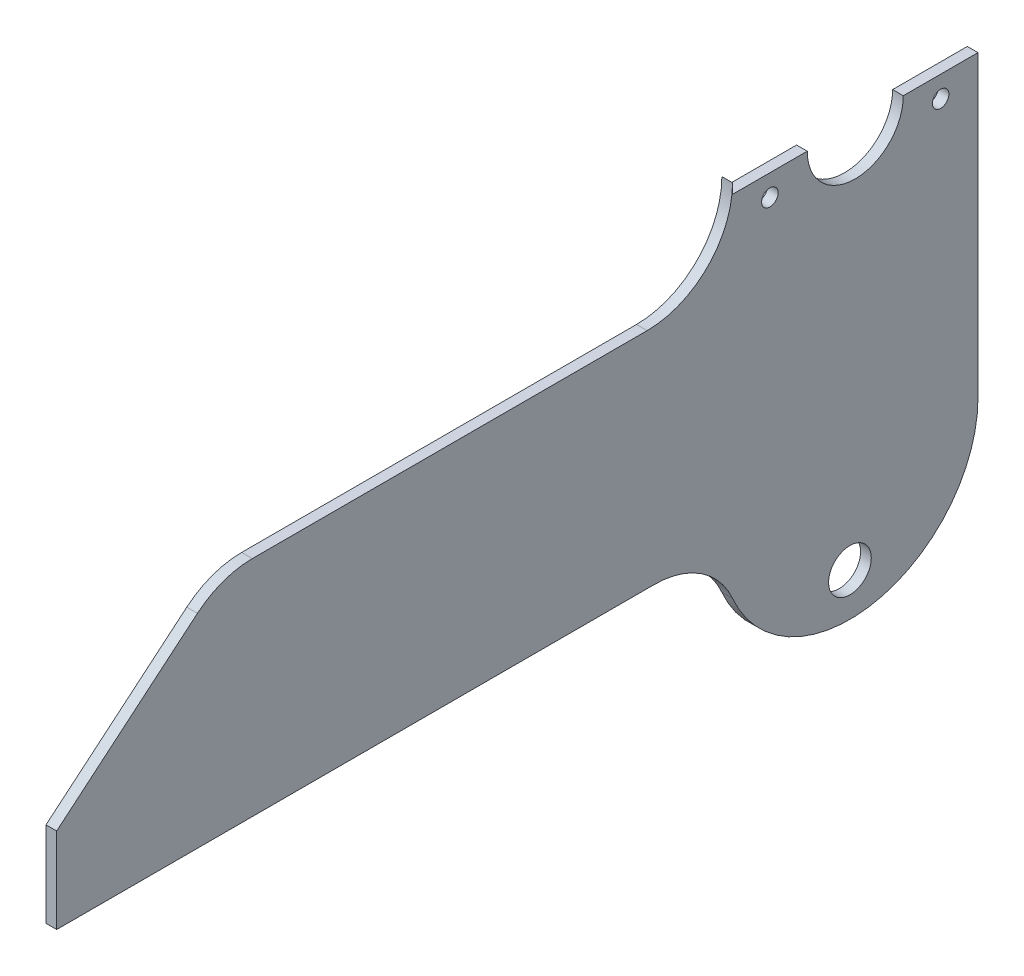
SolidWorks part; units mm, degrees
material "6061 Alloy"
ref_plane "Front Plane" through (0, 0, 0) normal (0, 0, 1) x (1, 0, 0)
ref_plane "Top Plane" through (0, 0, 0) normal (0, 1, 0) x (1, 0, 0)
ref_plane "Right Plane" through (0, 0, 0) normal (1, 0, 0) x (0, 0, -1)
sketch "Sketch1" plane through (0, 0, 0) normal (1, 0, 0) x (0, 0, -1)
  line L0 (0, -44.45) -> (0, 44.45)
  line L7 (0, 44.45) -> (-22.225, 44.45)
  line L8 (-50.8, 44.45) -> (-73.025, 44.45)
  line L10 (-98.425, 22.0322) -> (-215.9, 22.0322)
  line L13 (-274.1047, -44.45) -> (-96.3047, -44.45)
  line L14 (-274.1047, -44.45) -> (-274.1047, -19.05)
  line L15 (-274.1047, -19.05) -> (-232.2268, 16.0897)
  line L16 (-274.1047, -19.05) -> (0, -19.05) construction
  line L17 (-96.3047, -44.45) -> (0, -44.45) construction
  line L18 (-73.025, 44.45) -> (-73.025, 47.4322)
  arc A2 (-22.225, 44.45) -> (-50.8, 44.45) centre (-36.5125, 44.45) cw
  arc A3 (-73.025, -59.6905) -> (0, -44.45) centre (-38.1029, -44.45) ccw
  arc A4 (-215.9, 22.0322) -> (-232.2268, 16.0897) centre (-215.9, -3.3678) ccw
  arc A5 (-96.3047, -44.45) -> (-73.025, -59.6905) centre (-96.3047, -69.85) cw
  arc A6 (-73.025, 47.4322) -> (-98.425, 22.0322) centre (-98.425, 47.4322) cw
  point P4 (0, 0)
  point P20 (-76.2057, -44.45)
  dimension "D1" = 28.575
  dimension "D4" = 25.4
  dimension "D7" = 25.4
  dimension "D2" = 88.9
  dimension "D3" = 73.025
  dimension "D5" = 117.475
  dimension "D6" = 177.8
  dimension "D8" = 50
extrude "Boss-Extrude1" add sketch "Sketch1" along normal blind 3.175
hole_wizard "#10 (0.1935) Diameter Hole1" positions "Sketch2" profile "Sketch3" hole size "#10" standard "ANSI Inch" end condition through all
sketch "Sketch2" plane through (3.175, 0, 0) normal (1, 0, 0) x (0, 0, -1)
  line L0 (-50.8, 44.45) -> (-73.025, 44.45) construction
  line L1 (-61.9125, 38.1) -> (-11.1125, 38.1) construction
  line L3 (-36.5125, 38.1) -> (-36.5125, 44.45) construction
  point P0 (-61.9125, 38.1)
  point P2 (-11.1125, 38.1)
  dimension "D1" = 50.8
  dimension "D2" = 6.35
sketch "Sketch3" plane through (3.175, 38.1, 61.9125) normal (0, 1, 0) x (0, 0, -1)
  line L0 (0, 0) -> (0, 3.175)
  line L1 (0, 3.175) -> (2.4574, 3.175)
  line L2 (2.4574, 3.175) -> (2.4574, 0)
  line L5 (2.4574, 0) -> (0, 0)
  line L11 (0, -6.35) -> (0, 107.95) construction
  dimension "Thru Hole Dia." = 4.9149
  dimension "Thru Hole Depth" = 3.175
sketch "Sketch4" plane through (3.175, 0, 0) normal (1, 0, 0) x (0, 0, -1)
  line L0 (-38.1029, -69.85) -> (-38.1029, -44.45) construction
  line L1 (-38.1029, -69.85) -> (-38.1029, -82.5529) construction
  circle A0 centre (-38.1029, -69.85) radius 6.35
  arc A2 (-73.025, -59.6905) -> (0, -44.45) centre (-38.1029, -44.45) ccw construction
  dimension "D1" = 12.7
  dimension "D2" = 25.4
  dimension "D3" = 12.7029
extrude "Cut-Extrude1" cut sketch "Sketch4" against normal through all
